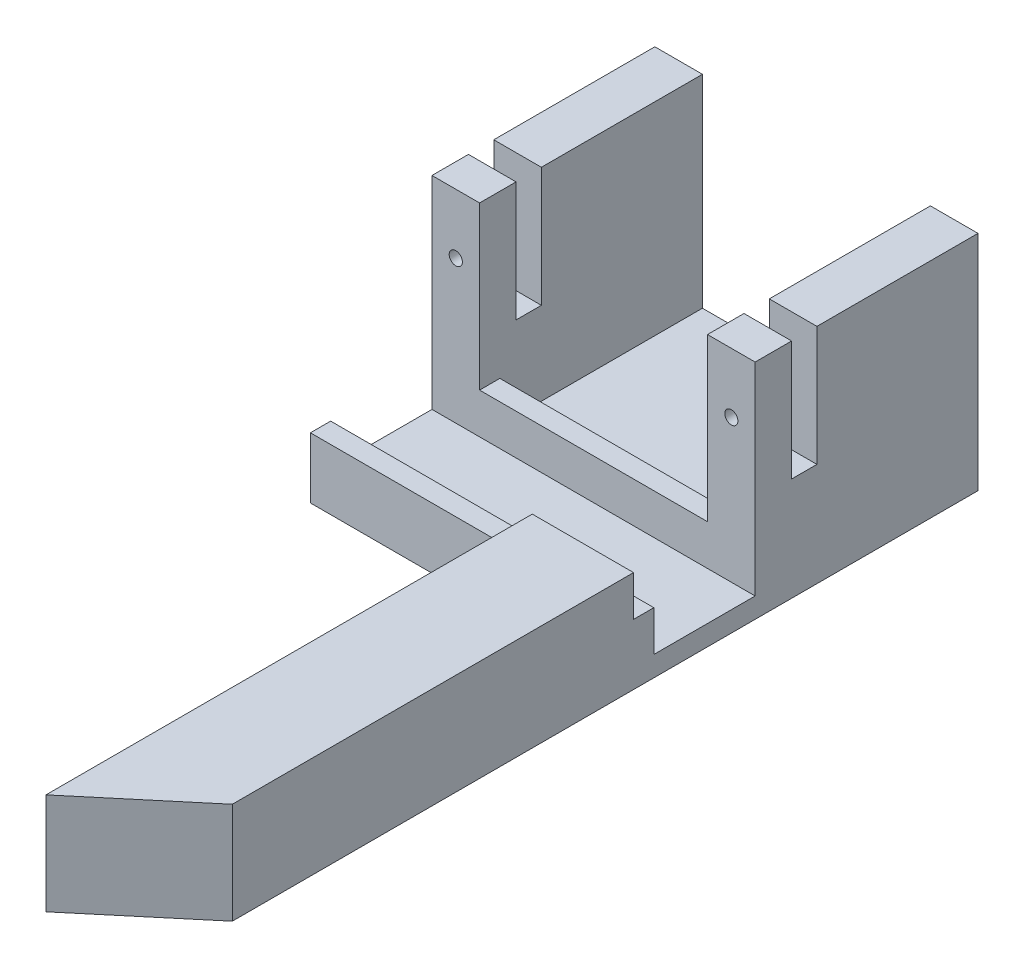
SolidWorks part; units mm, degrees
ref_plane "Front Plane" through (0, 0, 0) normal (0, 0, 1) x (1, 0, 0)
ref_plane "Top Plane" through (0, 0, 0) normal (0, 1, 0) x (1, 0, 0)
ref_plane "Right Plane" through (0, 0, 0) normal (1, 0, 0) x (0, 0, -1)
sketch "Sketch1" plane through (0, 0, 0) normal (0, 1, 0) x (1, 0, 0)
  line L1 (-15.95, 17) -> (15.95, 17)
  line L2 (-15.95, 17) -> (-15.95, -17)
  line L3 (-15.95, -17) -> (15.95, -17)
  line L4 (15.95, 17) -> (15.95, -17)
  line L5 (-15.95, 17) -> (15.95, -17) construction
  line L6 (-15.95, -17) -> (15.95, 17) construction
  point P0 (0, 0)
  dimension "D1" = 31.9
  dimension "D2" = 34
extrude "Boss-Extrude3" add sketch "Sketch1" along normal blind 2
sketch "Sketch2" plane through (0, 2, 0) normal (0, 1, 0) x (1, 0, 0)
  line L0 (0, 17) -> (0, -17) construction
  line L1 (-15.95, 17) -> (15.95, 17)
  line L2 (-15.95, 17) -> (-15.95, -17)
  line L3 (-15.95, -17) -> (15.95, -17)
  line L4 (15.95, 17) -> (15.95, -17)
  line L5 (-15.95, 17) -> (-11.25, 17)
  line L6 (-15.95, 17) -> (-15.95, -5)
  line L7 (-15.95, -5) -> (-11.25, -5)
  line L8 (-11.25, 17) -> (-11.25, -5)
  line L9 (15.95, -5) -> (11.25, -5)
  line L10 (11.25, 17) -> (11.25, -5)
  line L11 (15.95, 17) -> (11.25, 17)
  line L12 (15.95, 17) -> (15.95, -5)
  dimension "D1" = 4.7
  dimension "D2" = 22
  dimension "D3" = 22
  dimension "D5" = 4.7
extrude "Boss-Extrude4" add sketch "Sketch2" along normal blind 20 contours L6 L5 L8 L7 | L12 L9 L10 L11
sketch "Sketch3" plane through (0, 2, 0) normal (0, 1, 0) x (1, 0, 0)
  line L1 (-11.25, -5) -> (11.25, -5)
  line L2 (-11.25, -5) -> (-11.25, -3)
  line L3 (-11.25, -3) -> (11.25, -3)
  line L4 (11.25, -5) -> (11.25, -3)
  line L5 (-15.95, -17) -> (15.95, -17)
  line L6 (-15.95, -17) -> (-15.95, -15)
  line L7 (-15.95, -15) -> (15.95, -15)
  line L8 (15.95, -17) -> (15.95, -15)
  dimension "D1" = 22.5
  dimension "D2" = 2
  dimension "D3" = 2
  dimension "D4" = 31.9
extrude "Boss-Extrude5" add sketch "Sketch3" along normal blind 4
sketch "Sketch6" plane through (0, 22, 0) normal (0, 1, 0) x (1, 0, 0)
  line L0 (15.95, 17) -> (15.95, -5) construction
  line L1 (-15.95, 17) -> (15.95, 17)
  line L2 (-15.95, 17) -> (-15.95, -1.4)
  line L3 (-15.95, -1.4) -> (15.95, -1.4)
  line L4 (15.95, 17) -> (15.95, -1.4)
  line L6 (-15.95, -1.4) -> (15.95, -1.4)
  line L7 (-15.95, -1.4) -> (-15.95, 1.1)
  line L8 (-15.95, 1.1) -> (15.95, 1.1)
  line L9 (15.95, -1.4) -> (15.95, 1.1)
  line M10 (-11.25, -5) -> (-11.25, 17)
  dimension "D1" = 18.4
  dimension "D2" = 2.5
  dimension "D3" = 31.9
extrude "Cut-Extrude1" cut sketch "Sketch6" against normal blind 11.8 contours L8 L3 L4 M10 | L8 L2 L3 M10 region at (-13.6, 22, 0.15) region at (2.35, 22, 0.15)
sketch "Sketch7" plane through (0, 0, 5) normal (0, 0, 1) x (1, 0, 0)
  line L1 (-15.95, 22) -> (-11.25, 22) construction
  line L2 (-15.95, 22) -> (-15.95, 2) construction
  line L3 (15.95, 22) -> (11.25, 22) construction
  line L4 (11.25, 22) -> (11.25, 6) construction
  circle A0 centre (-13.6, 16.1) radius 0.65
  circle A1 centre (13.6, 16.1) radius 0.65
  point P22 (-13.6, 16.1)
  point P23 (13.6, 16.1)
  dimension "D3" = 1.3
  dimension "D4" = 1.3
  dimension "D1" = 5.9
  dimension "D2" = 2.35
  dimension "D5" = 5.9
  dimension "D6" = 2.35
extrude "Cut-Extrude2" cut sketch "Sketch7" against normal blind 4
sketch "Sketch8" plane through (0, 0, 0) normal (0, 1, 0) x (1, 0, 0)
  line L0 (5.95, -65) -> (15.95, -56.609)
  line L1 (15.95, -17) -> (5.95, -17)
  line L2 (15.95, -17) -> (15.95, -56.609)
  line L4 (5.95, -17) -> (5.95, -65)
  dimension "D1" = 60
extrude "Boss-Extrude6" add sketch "Sketch8" along normal blind 10 contours L2 L0 L4 L1
